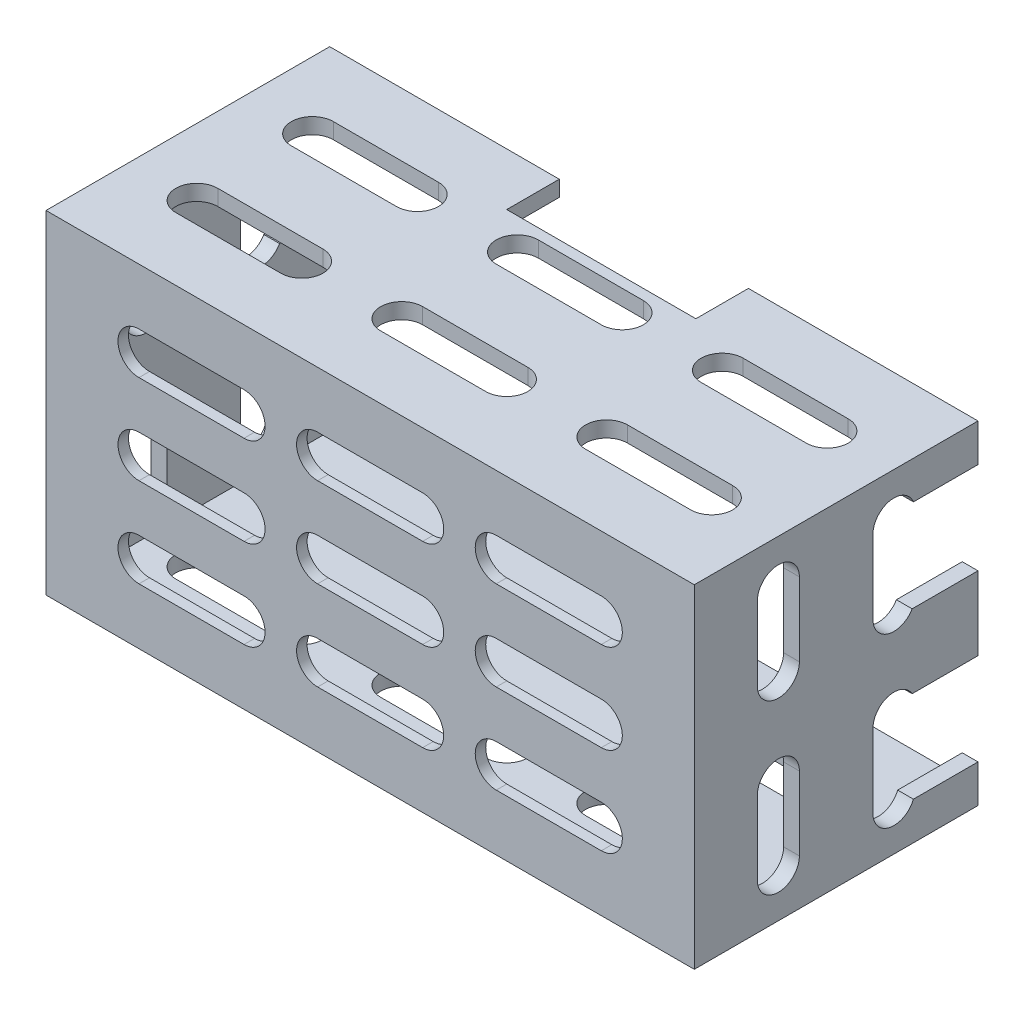
SolidWorks part; units mm, degrees
ref_plane "Front Plane" through (0, 0, 0) normal (0, 0, 1) x (1, 0, 0)
ref_plane "Top Plane" through (0, 0, 0) normal (0, 1, 0) x (1, 0, 0)
ref_plane "Right Plane" through (0, 0, 0) normal (1, 0, 0) x (0, 0, -1)
sketch "Sketch1" plane through (0, 0, 0) normal (0, 0, 1) x (1, 0, 0)
  line L4 (29.35, -14.35) -> (-29.35, -14.35)
  line L5 (29.25, -14.25) -> (-29.25, -14.25) construction
  line L6 (29.25, -14.25) -> (29.25, 14.25) construction
  line L7 (29.25, 14.25) -> (-29.25, 14.25) construction
  line L16 (-29.25, -14.25) -> (-29.25, 14.25) construction
  line L17 (-29.35, -14.35) -> (-29.35, 14.35)
  line L18 (29.35, 14.35) -> (-29.35, 14.35)
  line L19 (29.35, -14.35) -> (29.35, 14.35)
  line L20 (-30.85, -15.85) -> (-30.85, 15.85)
  line L21 (30.85, 15.85) -> (-30.85, 15.85)
  line L22 (30.85, -15.85) -> (30.85, 15.85)
  line L23 (30.85, -15.85) -> (-30.85, -15.85)
  point P4 (29.25, -14.25)
  dimension "D1" = 0.1
  dimension "D2" = 1.5
extrude "Boss-Extrude1" add sketch "Sketch1" along normal blind 21
sketch "Sketch2" plane through (0, 0, 21) normal (0, 0, 1) x (1, 0, 0)
  line L4 (-30.85, -15.85) -> (30.85, -15.85)
  line L5 (-30.85, -15.85) -> (30.85, -15.85)
  line L6 (-30.85, 15.85) -> (-30.85, -15.85)
  line L7 (30.85, 15.85) -> (-30.85, 15.85)
  line L10 (-30.85, 15.85) -> (-30.85, -15.85)
  line L11 (30.85, 15.85) -> (-30.85, 15.85)
  line L12 (30.85, -15.85) -> (30.85, 15.85)
  line L13 (30.85, -15.85) -> (30.85, 15.85)
  dimension "D1" = 0
extrude "Boss-Extrude2" add sketch "Sketch2" along normal blind 1
sketch "Sketch3" plane through (0, 0, 0) normal (0, 0, -1) x (-1, 0, 0)
  line L1 (29.35, -14.35) -> (-29.35, -14.35) construction
  line L4 (-30.85, -15.85) -> (30.85, -15.85)
  line L5 (30.85, 15.85) -> (-30.85, 15.85)
  line L6 (30.85, -15.85) -> (30.85, 15.85)
  line L7 (-30.85, -15.85) -> (30.85, -15.85)
  line L9 (30.85, 15.85) -> (9, 15.85)
  line L10 (30.85, -15.85) -> (30.85, 15.85)
  line L14 (29.35, 14.35) -> (29.35, -14.35) construction
  line L20 (-29.35, 14.35) -> (29.35, 14.35) construction
  line L21 (-29.35, -14.35) -> (-29.35, 14.35) construction
  line L22 (29.35, -14.35) -> (-29.35, -14.35)
  line L23 (29.35, 14.35) -> (29.35, -14.35)
  line L24 (-30.85, 15.85) -> (-30.85, -15.85)
  line L25 (-30.85, 15.85) -> (-30.85, -15.85)
  line L26 (-29.35, 14.35) -> (-9, 14.35)
  line L27 (-29.35, -14.35) -> (-29.35, 14.35)
  line L28 (-9, 14.35) -> (-9, 15.85)
  line L29 (9, 14.35) -> (9, 15.85)
  line L30 (-9, 15.85) -> (-30.85, 15.85)
  line L31 (9, 14.35) -> (29.35, 14.35)
  point P10 (9, 15.1)
  dimension "D2" = 18
  dimension "D1" = 0
extrude "Boss-Extrude3" add sketch "Sketch3" along normal up to surface (5 mm away)
sketch "Sketch8" plane through (0, 0, 21) normal (0, 0, -1) x (-1, 0, 0)
  line L0 (12, 6.5) -> (22, 6.5) construction
  line L1 (12, -2) -> (22, -2) construction
  line L2 (12, -10.5) -> (22, -10.5) construction
  line L3 (-5, -10.5) -> (5, -10.5) construction
  line L4 (-22, -10.5) -> (-12, -10.5) construction
  line L5 (-22, -2) -> (-12, -2) construction
  line L6 (-5, 6.5) -> (5, 6.5) construction
  line L7 (-22, 6.5) -> (-12, 6.5) construction
  line L8 (12, 6.5) -> (22, 6.5)
  line L9 (12, -2) -> (22, -2)
  line L10 (12, -10.5) -> (22, -10.5)
  line L11 (-5, -10.5) -> (5, -10.5)
  line L12 (-22, -10.5) -> (-12, -10.5)
  line L13 (-22, -2) -> (-12, -2)
  line L14 (-5, 6.5) -> (5, 6.5)
  line L15 (-22, 6.5) -> (-12, 6.5)
  line L16 (22, -6.5) -> (12, -6.5) construction
  line L17 (5, -6.5) -> (-5, -6.5) construction
  line L18 (-12, -6.5) -> (-22, -6.5) construction
  line L19 (22, 2) -> (12, 2) construction
  line L20 (-5, -2) -> (5, -2) construction
  line L21 (5, 2) -> (-5, 2) construction
  line L22 (-12, 2) -> (-22, 2) construction
  line L23 (22, 10.5) -> (12, 10.5) construction
  line L24 (5, 10.5) -> (-5, 10.5) construction
  line L25 (-12, 10.5) -> (-22, 10.5) construction
  line L26 (22, -6.5) -> (12, -6.5)
  line L27 (5, -6.5) -> (-5, -6.5)
  line L28 (-12, -6.5) -> (-22, -6.5)
  line L29 (22, 2) -> (12, 2)
  line L30 (-5, -2) -> (5, -2)
  line L31 (5, 2) -> (-5, 2)
  line L32 (-12, 2) -> (-22, 2)
  line L33 (22, 10.5) -> (12, 10.5)
  line L34 (5, 10.5) -> (-5, 10.5)
  line L35 (-12, 10.5) -> (-22, 10.5)
  arc A0 (22, -10.5) -> (22, -6.5) centre (22, -8.5) ccw construction
  arc A1 (12, -6.5) -> (12, -10.5) centre (12, -8.5) ccw construction
  arc A2 (5, -10.5) -> (5, -6.5) centre (5, -8.5) ccw construction
  arc A3 (-5, -6.5) -> (-5, -10.5) centre (-5, -8.5) ccw construction
  arc A4 (-12, -10.5) -> (-12, -6.5) centre (-12, -8.5) ccw construction
  arc A5 (-22, -6.5) -> (-22, -10.5) centre (-22, -8.5) ccw construction
  arc A6 (22, -2) -> (22, 2) centre (22, 0) ccw construction
  arc A7 (12, 2) -> (12, -2) centre (12, 0) ccw construction
  arc A8 (-5, 2) -> (-5, -2) centre (-5, 0) ccw construction
  arc A9 (5, -2) -> (5, 2) centre (5, 0) ccw construction
  arc A10 (-12, -2) -> (-12, 2) centre (-12, 0) ccw construction
  arc A11 (-22, 2) -> (-22, -2) centre (-22, 0) ccw construction
  arc A12 (22, 6.5) -> (22, 10.5) centre (22, 8.5) ccw construction
  arc A13 (12, 10.5) -> (12, 6.5) centre (12, 8.5) ccw construction
  arc A14 (-5, 10.5) -> (-5, 6.5) centre (-5, 8.5) ccw construction
  arc A15 (-12, 6.5) -> (-12, 10.5) centre (-12, 8.5) ccw construction
  arc A16 (-22, 10.5) -> (-22, 6.5) centre (-22, 8.5) ccw construction
  arc A17 (22, -10.5) -> (22, -6.5) centre (22, -8.5) ccw
  arc A18 (12, -6.5) -> (12, -10.5) centre (12, -8.5) ccw
  arc A19 (5, -10.5) -> (5, -6.5) centre (5, -8.5) ccw
  arc A20 (-5, -6.5) -> (-5, -10.5) centre (-5, -8.5) ccw
  arc A21 (-12, -10.5) -> (-12, -6.5) centre (-12, -8.5) ccw
  arc A22 (-22, -6.5) -> (-22, -10.5) centre (-22, -8.5) ccw
  arc A23 (22, -2) -> (22, 2) centre (22, 0) ccw
  arc A24 (12, 2) -> (12, -2) centre (12, 0) ccw
  arc A25 (-5, 2) -> (-5, -2) centre (-5, 0) ccw
  arc A26 (5, -2) -> (5, 2) centre (5, 0) ccw
  arc A27 (-12, -2) -> (-12, 2) centre (-12, 0) ccw
  arc A28 (-22, 2) -> (-22, -2) centre (-22, 0) ccw
  arc A29 (22, 6.5) -> (22, 10.5) centre (22, 8.5) ccw
  arc A30 (12, 10.5) -> (12, 6.5) centre (12, 8.5) ccw
  arc A31 (-5, 10.5) -> (-5, 6.5) centre (-5, 8.5) ccw
  arc A32 (-12, 6.5) -> (-12, 10.5) centre (-12, 8.5) ccw
  arc A33 (-22, 10.5) -> (-22, 6.5) centre (-22, 8.5) ccw
  arc A34 (5, 6.5) -> (5, 10.5) centre (5, 8.5) ccw construction
  arc A35 (5, 6.5) -> (5, 10.5) centre (5, 8.5) ccw
extrude "Cut-Extrude4" cut sketch "Sketch8" against normal through all
sketch "Sketch5" plane through (-15, 15.85, 0) normal (0, -1, 0) x (1, 0, 0)
  line L0 (-9.5, 3) -> (0.5, 3) construction
  line L1 (-9.5, 5) -> (0.5, 5)
  line L2 (-9.5, 1) -> (0.5, 1)
  line L3 (-15.85, 8.5) -> (45.85, 8.5) construction
  line L4 (45.85, -5) -> (-15.85, -5) construction
  line L5 (-15.85, 22) -> (45.85, 22) construction
  line L6 (15, -5) -> (15, 22) construction
  line L7 (45.85, 14) -> (-15.85, 14) construction
  line L8 (-15.85, 22) -> (-15.85, -5) construction
  line L9 (-4.5, 22) -> (-4.5, -5) construction
  line L10 (45.85, 3) -> (-15.85, 3) construction
  line L11 (34.5, 22) -> (34.5, -5) construction
  line L13 (10, 1) -> (20, 1)
  line L14 (10, 5) -> (20, 5)
  line L15 (10, 3) -> (20, 3) construction
  line L16 (29.5, 1) -> (39.5, 1)
  line L17 (29.5, 5) -> (39.5, 5)
  line L18 (29.5, 3) -> (39.5, 3) construction
  line L19 (10, 12) -> (20, 12)
  line L20 (10, 16) -> (20, 16)
  line L21 (10, 14) -> (20, 14) construction
  line L22 (29.5, 12) -> (39.5, 12)
  line L23 (29.5, 16) -> (39.5, 16)
  line L24 (29.5, 14) -> (39.5, 14) construction
  line L25 (-9.5, 12) -> (0.5, 12)
  line L26 (-9.5, 16) -> (0.5, 16)
  line L27 (-9.5, 14) -> (0.5, 14) construction
  line L28 (45.85, 22) -> (45.85, -5) construction
  arc A0 (-9.5, 5) -> (-9.5, 1) centre (-9.5, 3) ccw
  arc A1 (0.5, 1) -> (0.5, 5) centre (0.5, 3) ccw
  arc A2 (10, 5) -> (10, 1) centre (10, 3) ccw
  arc A3 (20, 1) -> (20, 5) centre (20, 3) ccw
  arc A4 (29.5, 5) -> (29.5, 1) centre (29.5, 3) ccw
  arc A5 (39.5, 1) -> (39.5, 5) centre (39.5, 3) ccw
  arc A6 (10, 16) -> (10, 12) centre (10, 14) ccw
  arc A7 (20, 12) -> (20, 16) centre (20, 14) ccw
  arc A8 (29.5, 16) -> (29.5, 12) centre (29.5, 14) ccw
  arc A9 (39.5, 12) -> (39.5, 16) centre (39.5, 14) ccw
  arc A10 (-9.5, 16) -> (-9.5, 12) centre (-9.5, 14) ccw
  arc A11 (0.5, 12) -> (0.5, 16) centre (0.5, 14) ccw
  point P2 (-4.5, 3)
  point P9 (0, 0)
  point P15 (45.85, 8.5)
  point P17 (0, 0)
  point P18 (0, 0)
  point P21 (0.5, 16)
  point P25 (0, 0)
  point P29 (15, -5)
  point P31 (15, 3)
  point P38 (34.5, 3)
  point P45 (15, 14)
  point P52 (34.5, 14)
  point P59 (-4.5, 14)
  point P64 (15, 22)
  point P67 (-15.85, 8.5)
  point P68 (0, 0)
  point P71 (-15.85, 8.5)
  point P74 (0, 0)
  dimension "D1" = 10
  dimension "D2" = 4
  dimension "D3" = 39
  dimension "D4" = 11
  dimension "D5" = 3
  dimension "D6" = 2
extrude "Cut-Extrude2" cut sketch "Sketch5" along normal through all
sketch "Sketch7" plane through (30.85, -15, 0) normal (-1, 0, 0) x (0, 0, -1)
  line L0 (-14, -26.5) -> (-14, -19.5) construction
  line L1 (-16, -26.5) -> (-16, -19.5)
  line L2 (-12, -26.5) -> (-12, -19.5)
  line L3 (-22, -15) -> (5, -15) construction
  line L4 (-22, -30.85) -> (-22, 0.85) construction
  line L5 (5, 0.85) -> (5, -30.85) construction
  line L6 (-8.5, 0.85) -> (-8.5, -30.85) construction
  line L7 (-22, 0.85) -> (5, 0.85) construction
  line L8 (-22, -30.85) -> (5, -30.85) construction
  line L9 (-14, -30.85) -> (-14, 0.85) construction
  line L10 (-22, -7) -> (5, -7) construction
  line L11 (-22, -23) -> (5, -23) construction
  line L12 (-3, -30.85) -> (-3, 0.85) construction
  line L13 (-1, -26.5) -> (-1, -19.5)
  line L14 (-5, -26.5) -> (-5, -19.5)
  line L15 (-3, -26.5) -> (-3, -19.5) construction
  line L16 (-1, -10.5) -> (-1, -3.5)
  line L17 (-5, -10.5) -> (-5, -3.5)
  line L18 (-3, -10.5) -> (-3, -3.5) construction
  line L19 (-12, -10.5) -> (-12, -3.5)
  line L20 (-16, -10.5) -> (-16, -3.5)
  line L21 (-14, -10.5) -> (-14, -3.5) construction
  arc A0 (-16, -26.5) -> (-12, -26.5) centre (-14, -26.5) ccw
  arc A1 (-12, -19.5) -> (-16, -19.5) centre (-14, -19.5) ccw
  arc A2 (-5, -26.5) -> (-1, -26.5) centre (-3, -26.5) ccw
  arc A3 (-1, -19.5) -> (-5, -19.5) centre (-3, -19.5) ccw
  arc A4 (-5, -10.5) -> (-1, -10.5) centre (-3, -10.5) ccw
  arc A5 (-1, -3.5) -> (-5, -3.5) centre (-3, -3.5) ccw
  arc A6 (-16, -10.5) -> (-12, -10.5) centre (-14, -10.5) ccw
  arc A7 (-12, -3.5) -> (-16, -3.5) centre (-14, -3.5) ccw
  point P2 (-14, -23)
  point P9 (0, 0)
  point P10 (-22, -23.3553)
  point P15 (6.5139, -15)
  point P16 (-22, -15)
  point P27 (0, 0)
  point P32 (-3, -23)
  point P39 (-3, -7)
  point P46 (-14, -7)
  point P51 (0, 0)
  point P54 (0, 0)
  dimension "D1" = 7
  dimension "D2" = 4
  dimension "D3" = 16
  dimension "D6" = 11
  dimension "D4" = 2
  dimension "D5" = 2
extrude "Cut-Extrude3" cut sketch "Sketch7" along normal through all
sketch "Sketch9" plane through (-30.85, 0, 0) normal (-1, 0, 0) x (0, 0, 1)
  line L0 (-5, 0) -> (22, 0) construction
  line L1 (-5, 3.5) -> (3, 3.5)
  line L2 (-5, 3.5) -> (-5, 12.25)
  line L3 (-5, 12.25) -> (3, 12.25)
  line L4 (3, 3.5) -> (3, 12.25)
  line L6 (-5, -15.85) -> (-5, 15.85) construction
  line L7 (22, 15.85) -> (22, -15.85) construction
  line L8 (3, -3.5) -> (3, -12.25)
  line L9 (-5, -12.25) -> (3, -12.25)
  line L10 (-5, -3.5) -> (-5, -12.25)
  line L11 (-5, -3.5) -> (3, -3.5)
  arc A0 (5, 11.5) -> (1, 11.5) centre (3, 11.5) ccw construction
  point P11 (3.0767, 12.25)
  point P22 (3, 13.5)
  point P23 (0, 0)
  point P25 (0, 0)
  point P26 (0, 0)
  point P27 (-5, 4.6491)
  point P28 (0, 0)
extrude "Cut-Extrude5" cut sketch "Sketch9" against normal through all
